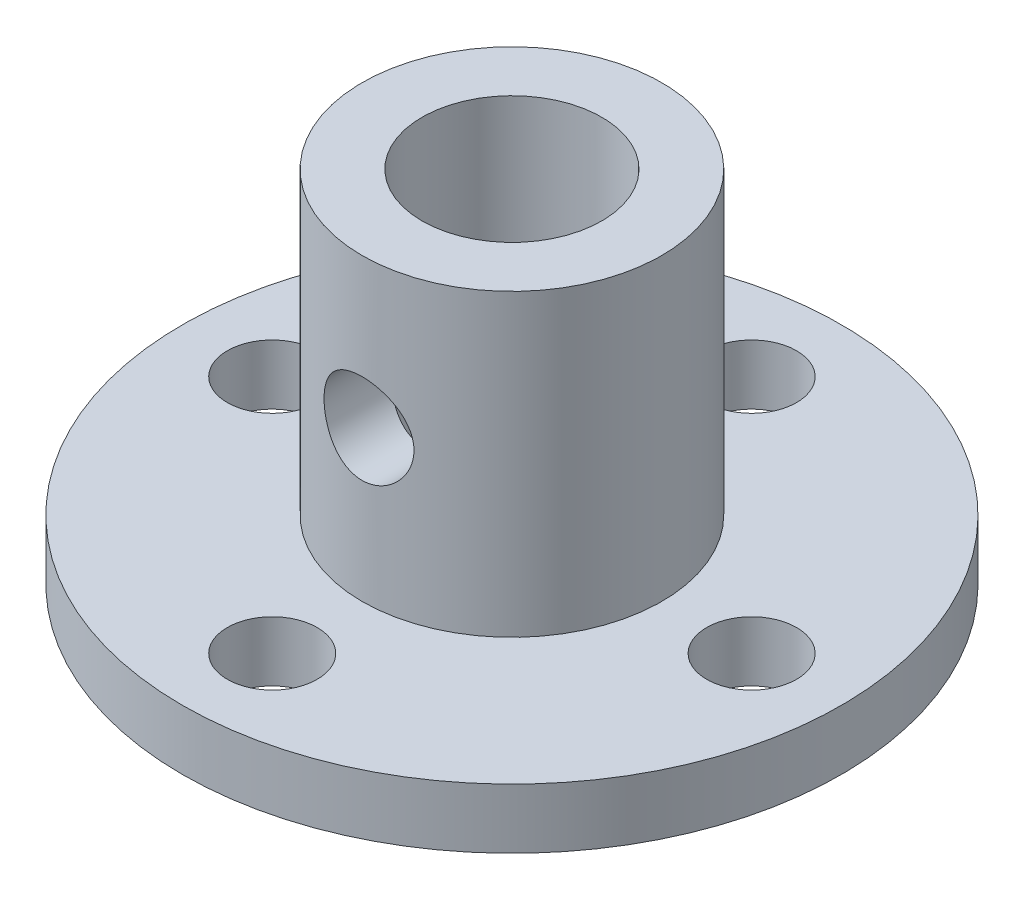
SolidWorks part; units mm, degrees
material "不锈钢 (铁素体)"
ref_plane "前视基准面" through (0, 0, 0) normal (0, 0, 1) x (1, 0, 0)
ref_plane "上视基准面" through (0, 0, 0) normal (0, 1, 0) x (1, 0, 0)
ref_plane "右视基准面" through (0, 0, 0) normal (1, 0, 0) x (0, 0, -1)
other "Configuration Table"
sketch "草图1" plane through (0, 0, 0) normal (0, 1, 0) x (1, 0, 0)
  circle A0 centre (0, 0) radius 11
extrude "凸台-拉伸1" add sketch "草图1" along normal blind 2
sketch "草图2" plane through (0, 0, 0) normal (0, -1, 0) x (1, 0, 0)
  circle A0 centre (0, 0) radius 8 construction
  circle A1 centre (0, -8) radius 1.5
  circle A2 centre (8, 0) radius 1.5
  circle A3 centre (-8, 0) radius 1.5
  circle A4 centre (0, 8) radius 1.5
  dimension "D1" = 3
  dimension "D2" = 16
extrude "切除-拉伸1" cut sketch "草图2" against normal blind 2
sketch "草图3" plane through (0, 2, 0) normal (0, 1, 0) x (1, 0, 0)
  circle A0 centre (0, 0) radius 5
extrude "凸台-拉伸2" add sketch "草图3" along normal blind 10
sketch "草图4" plane through (0, 12, 0) normal (0, 1, 0) x (1, 0, 0)
  circle A0 centre (0, 0) radius 3
  dimension "D1" = 6
extrude "切除-拉伸2" cut sketch "草图4" against normal blind 12
sketch "草图5" plane through (0, 0, 0) normal (0, 0, 1) x (1, 0, 0)
  line L0 (0, 2) -> (0, 12) construction
  line L1 (11, 2) -> (-11, 2) construction
  line L2 (5, 12) -> (-5, 12) construction
  circle A0 centre (0, 7) radius 1.5
  dimension "D1" = 3
extrude "切除-拉伸4" cut sketch "草图5" against normal blind 5 and the other way blind 5
ref_plane "基准面1" through (0, 0, 5) normal (0, 0, 1) x (1, 0, 0)
